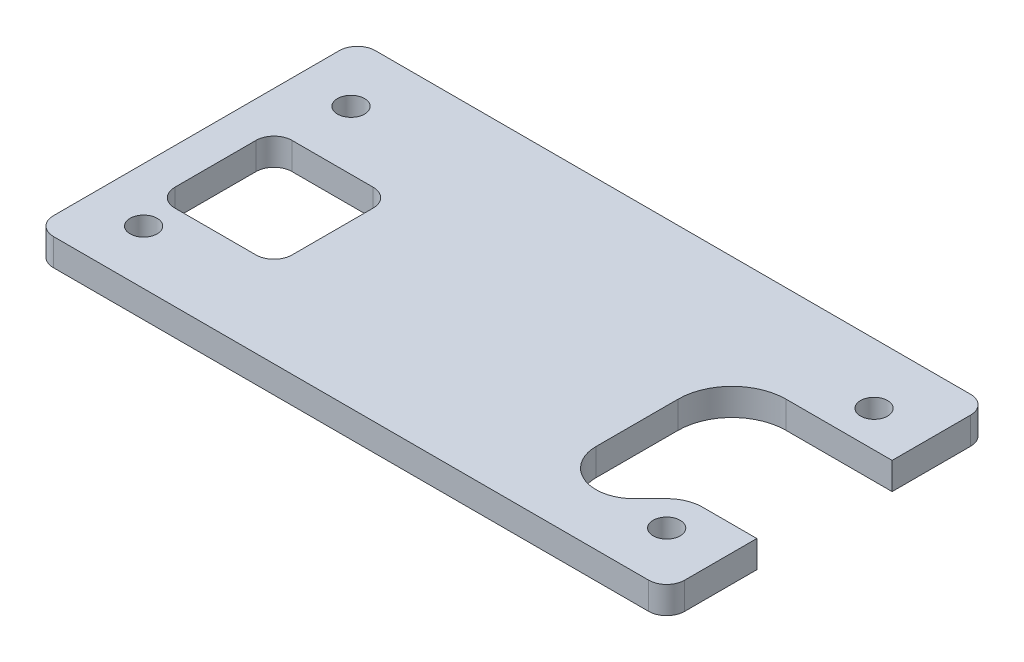
SolidWorks part; units mm, degrees
ref_plane "Front Plane" through (0, 0, 0) normal (0, 0, 1) x (1, 0, 0)
ref_plane "Top Plane" through (0, 0, 0) normal (0, 1, 0) x (1, 0, 0)
ref_plane "Right Plane" through (0, 0, 0) normal (1, 0, 0) x (0, 0, -1)
sketch "Sketch1" plane through (0, 0, 0) normal (0, 1, 0) x (1, 0, 0)
  line L0 (-35, 17.85) -> (35, 17.85)
  line L1 (-32.5, -15.35) -> (32.5, -15.35) construction
  line L2 (-32.5, -15.35) -> (-32.5, 15.35) construction
  line L3 (-32.5, 15.35) -> (32.5, 15.35) construction
  line L4 (32.5, -15.35) -> (32.5, 15.35) construction
  line L5 (0, 15.35) -> (0, -15.35) construction
  line L6 (-32.5, 0) -> (32.5, 0) construction
  line L11 (35, -17.85) -> (35, 17.85)
  line L12 (-35, -17.85) -> (35, -17.85)
  line L13 (-35, -17.85) -> (-35, 17.85)
  line L15 (-29, -11.85) -> (29, -11.85) construction
  line L16 (-29, -11.85) -> (-29, 11.15) construction
  line L17 (-29, 11.15) -> (29, 11.15) construction
  line L18 (29, -11.85) -> (29, 11.15) construction
  line L19 (0, 11.15) -> (0, -11.85) construction
  line L20 (-29, -0.35) -> (29, -0.35) construction
  circle A0 centre (-29, -11.85) radius 1.5
  circle A1 centre (29, -11.85) radius 1.5
  circle A2 centre (29, 11.15) radius 1.5
  circle A3 centre (-29, 11.15) radius 1.5
  point P0 (0, 0)
  point P8 (0, -0.35)
  point P16 (0, 0)
  point P17 (-29, -11.2325)
  dimension "D4" = 3
  dimension "D1" = 65
  dimension "D2" = 30.7
  dimension "D5" = 3.5
  dimension "D6" = 4.2
  dimension "D7" = 3.5
  dimension "D8" = 23
  dimension "D9" = 58
  dimension "D3" = 2.5
extrude "Boss-Extrude1" add sketch "Sketch1" along normal blind 3
sketch "Sketch2" plane through (0, 3, 0) normal (0, 1, 0) x (1, 0, 0)
  line L0 (-18, -8.39) -> (-31, -8.39)
  line L1 (-19.5, -6.89) -> (-29.5, -6.89) construction
  line L2 (-19.5, -6.89) -> (-19.5, 3.11) construction
  line L3 (-19.5, 3.11) -> (-29.5, 3.11) construction
  line L4 (-29.5, -6.89) -> (-29.5, 3.11) construction
  line L5 (-24.5, 3.11) -> (-24.5, -6.89) construction
  line L6 (-19.5, -1.89) -> (-29.5, -1.89) construction
  line L7 (-31, -8.39) -> (-31, 4.61)
  line L8 (-18, 4.61) -> (-31, 4.61)
  line L9 (-18, -8.39) -> (-18, 4.61)
  line L10 (-32.5, -15.35) -> (32.5, -15.35) construction
  line L11 (-32.5, -15.35) -> (-32.5, 15.35) construction
  line L12 (32.5, -15.35) -> (32.5, 15.35) construction
  line L13 (17.25, 1.15) -> (17.25, -7.9341)
  line L14 (24.3274, -10.8657) -> (26.1716, -9.0216)
  line L15 (29, -7.85) -> (35, -7.85)
  line L16 (35, -7.85) -> (35, 7.15)
  line L17 (35, 7.15) -> (23.25, 7.15)
  line L18 (35, -17.85) -> (35, 17.85) construction
  circle A0 centre (21.25, -6.08) radius 3 construction
  circle A1 centre (28.59, 0.4) radius 3 construction
  circle A2 centre (29, -11.85) radius 4 construction
  circle A3 centre (29, -11.85) radius 1.5 construction
  arc A4 (24.3274, -10.8657) -> (17.25, -7.9341) centre (21.3959, -7.9341) cw
  circle A5 centre (29, 11.15) radius 4 construction
  circle A6 centre (29, 11.15) radius 1.5 construction
  arc A7 (29, -7.85) -> (26.1716, -9.0216) centre (29, -11.85) ccw
  arc A8 (23.25, 7.15) -> (17.25, 1.15) centre (23.25, 1.15) ccw
  point P0 (-24.5, -1.89)
  point P20 (18.25, -6.08)
  point P25 (21.3959, -12.08)
  point P28 (21.25, -9.08)
  dimension "D9" = 6
  dimension "D11" = 8
  dimension "D14" = 6
  dimension "D2" = 10
  dimension "D3" = 13.46
  dimension "D4" = 8
  dimension "D5" = 15.75
  dimension "D6" = 3.91
  dimension "D7" = 11.25
  dimension "D8" = 9.27
  dimension "D10" = 1
  dimension "D12" = 45
  dimension "D13" = 3
  dimension "D1" = 1.5
extrude "Cut-Extrude1" cut sketch "Sketch2" against normal through all
fillet "Fillet1" radius 2 4 edges at (-18, 1.5, 8.39) (-31, 1.5, 8.39) (-18, 1.5, -4.61) (-31, 1.5, -4.61)
fillet "Fillet2" radius 2 4 edges at (35, 1.5, -17.85) (35, 1.5, 17.85) (-35, 1.5, 17.85) (-35, 1.5, -17.85)
